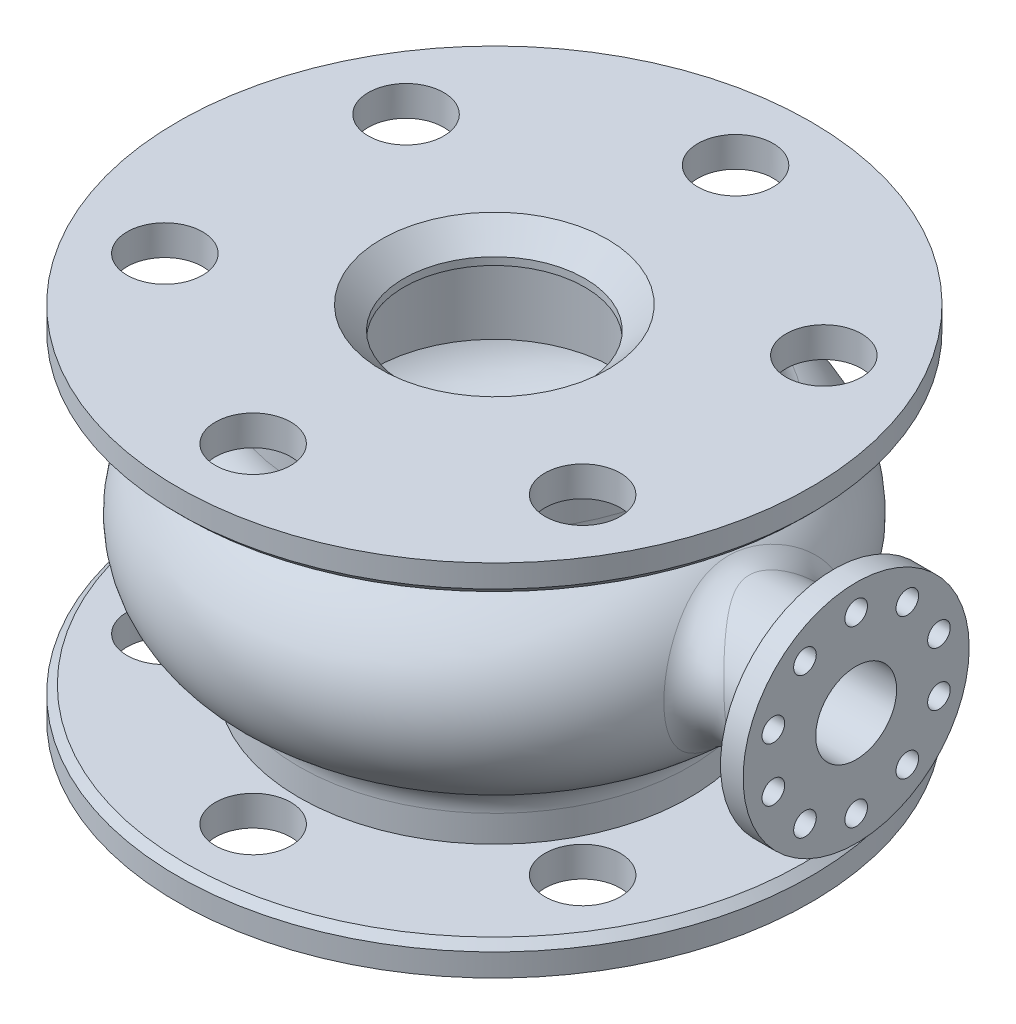
SolidWorks part; units mm, degrees
ref_plane "Front Plane" through (0, 0, 0) normal (0, 0, 1) x (1, 0, 0)
ref_plane "Top Plane" through (0, 0, 0) normal (0, 1, 0) x (1, 0, 0)
ref_plane "Right Plane" through (0, 0, 0) normal (1, 0, 0) x (0, 0, -1)
sketch "Sketch1" plane through (0, 0, 0) normal (0, 0, 1) x (1, 0, 0)
  line L0 (0, 0) -> (0, 51.3358) construction
  line L1 (12, -4.1952) -> (42, -4.1952)
  line L2 (12, 43.5) -> (42, 43.5)
  line L3 (12, 43.5) -> (12, 39.5)
  line L4 (12, 39.5) -> (15.9137, 39.5)
  line L5 (42, 43.5) -> (42, 39.5)
  line L6 (12, 43.5) -> (42, 39.5) construction
  line L7 (12, 39.5) -> (42, 43.5) construction
  line L12 (42, -0.1952) -> (42, -4.1952)
  line L13 (12, -0.1952) -> (15.9137, -0.1952)
  line L14 (12, -0.1952) -> (12, -4.1952)
  line L15 (25.9137, 39.5) -> (25.9137, 32.1265)
  line L16 (15.9137, 39.5) -> (15.9137, 28.2507)
  line L17 (25.9137, 7.0899) -> (25.9137, -0.1952)
  line L18 (25.9137, 39.5) -> (42, 39.5)
  line L19 (25.9137, -0.1952) -> (42, -0.1952) construction
  line L20 (15.9137, 10.9499) -> (15.9137, -0.1952)
  line L21 (25.8408, 10.9499) -> (15.9137, 10.9499)
  line L23 (25.9137, 28.2507) -> (15.9137, 28.2507)
  line L25 (25.9137, -0.1952) -> (42, -0.1952)
  arc A0 (25.9137, 32.1265) -> (25.9137, 7.0899) centre (24.0176, 19.6082) cw
  arc A1 (25.9137, 28.2507) -> (25.8408, 10.9499) centre (24.0176, 19.6082) cw
  point P3 (27, 41.5)
  point P19 (25.9475, 24.6318)
  dimension "D1" = 30
  dimension "D4" = 4
  dimension "D6" = 10
  dimension "D5" = 2
revolve "Revolve1" add sketch "Sketch1" angle 360 about L0 region at (12.5635, -2.1952, 0)
chamfer "Chamfer1" distance 3 angle 45 2 edges at (0, -4.1952, -12) (0, 43.5, -12)
sketch "Sketch2" plane through (0, 43.5, 0) normal (0, 1, 0) x (1, 0, 0)
  circle A0 centre (0, 32) radius 5
  circle A1 centre (27.7128, 16) radius 5
  circle A2 centre (27.7128, -16) radius 5
  circle A3 centre (0, -32) radius 5
  circle A4 centre (-27.7128, -16) radius 5
  circle A5 centre (-27.7128, 16) radius 5
  point P16 (0, 0)
  dimension "D1" = 10
  dimension "D2" = 32
  dimension "D3" = 6
extrude "Cut-Extrude1" cut sketch "Sketch2" against normal blind 10
extrude "Cut-Extrude2" cut sketch "Sketch2<3>" against normal blind 10 from surface starting at face at (0, -0.1952, -42)
sketch "Sketch2<3>" plane through (0, 43.5, 0) normal (0, 1, 0) x (1, 0, 0) same geometry as "Sketch2"
sketch "Sketch3" plane through (0, 0, 0) normal (1, 0, 0) x (0, 0, -1)
  circle A0 centre (0, 20.5763) radius 8.7364
  circle A1 centre (0, 20.5763) radius 5.3677
extrude "Boss-Extrude2" add sketch "Sketch3" against normal up to surface (9.4152 mm away) from offset 45 up to face at (0, 7.0899, -25.9137)
sketch "Sketch4" plane through (45, 0, 0) normal (1, 0, 0) x (0, 0, -1)
  circle A0 centre (0, 20.5763) radius 5.3677
extrude "Cut-Extrude3" cut sketch "Sketch4" against normal blind 31
sketch "Sketch5" plane through (45, 0, 0) normal (1, 0, 0) x (0, 0, -1)
  line L0 (25.9137, 32.1265) -> (-25.9137, 32.1265) construction
  circle A0 centre (0, 20.5763) radius 5.3677
  circle A1 centre (0, 20.5763) radius 15
  circle A2 centre (0, 32.1265) radius 1.5
  circle A3 centre (6.789, 29.9206) radius 1.5
  circle A4 centre (10.9848, 24.1455) radius 1.5
  circle A5 centre (10.9848, 17.0072) radius 1.5
  circle A6 centre (6.789, 11.2321) radius 1.5
  circle A7 centre (0, 9.0262) radius 1.5
  circle A8 centre (-6.789, 11.2321) radius 1.5
  circle A9 centre (-10.9848, 17.0072) radius 1.5
  circle A10 centre (-10.9848, 24.1455) radius 1.5
  circle A11 centre (-6.789, 29.9206) radius 1.5
  point P28 (0, 20.5763)
  dimension "D1" = 30
  dimension "D2" = 3
  dimension "D3" = 10
extrude "Boss-Extrude3" add sketch "Sketch5" along normal blind 3
chamfer "Chamfer2" distance 1 angle 45 2 edges at (0, -0.1952, -42) (0, 39.5, -42)
fillet "Fillet1" radius 5 1 edges at (33.279, 27.8496, 4.8399)
fillet "Fillet2" radius 5 2 edges at (0, 7.0899, -25.9137) (0, 32.1265, -25.9137)
